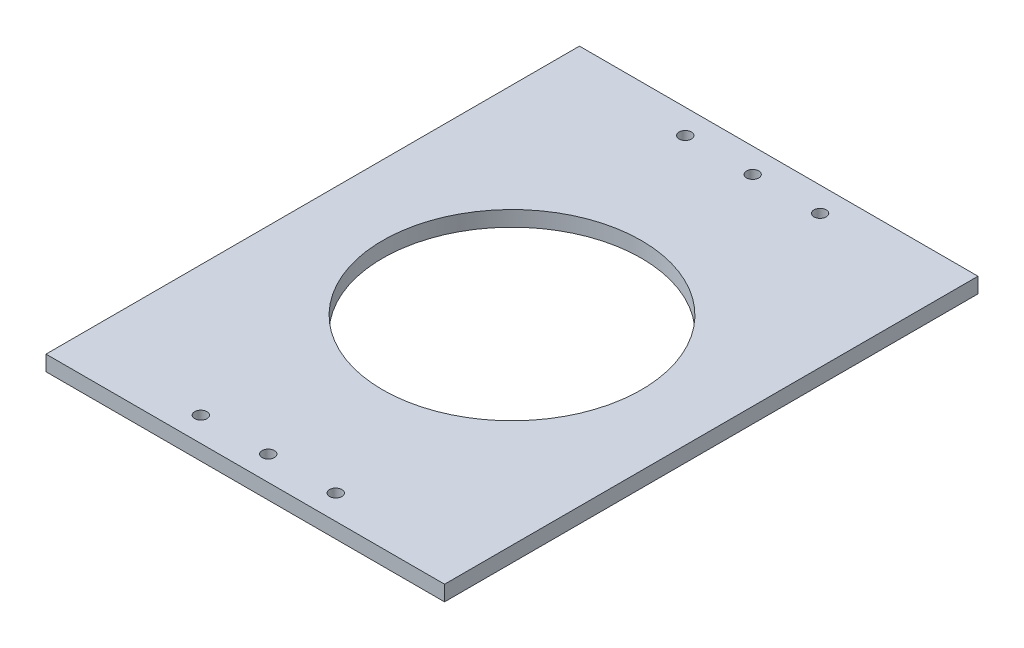
SolidWorks part; units mm, degrees
ref_plane "Front Plane" through (0, 0, 0) normal (0, 0, 1) x (1, 0, 0)
ref_plane "Top Plane" through (0, 0, 0) normal (0, 1, 0) x (1, 0, 0)
ref_plane "Right Plane" through (0, 0, 0) normal (1, 0, 0) x (0, 0, -1)
sketch "Sketch1" plane through (0, 0, 0) normal (0, 1, 0) x (1, 0, 0)
  line L0 (-276.663, 28.4247) -> (-130.5123, 28.4247) construction
  line L1 (-341.663, 115.4247) -> (-211.663, 115.4247)
  line L2 (-341.663, 115.4247) -> (-341.663, -58.5753)
  line L3 (-341.663, -58.5753) -> (-211.663, -58.5753)
  line L4 (-211.663, 115.4247) -> (-211.663, -58.5753)
  line L5 (-341.663, 115.4247) -> (-211.663, -58.5753) construction
  line L6 (-341.663, -58.5753) -> (-211.663, 115.4247) construction
  circle A0 centre (-276.663, 28.4247) radius 42.1979
  circle A1 centre (-299.163, 107.4247) radius 2
  circle A2 centre (-277.163, 107.4247) radius 2
  circle A3 centre (-255.163, 107.4247) radius 2
  circle A4 centre (-255.163, -50.5753) radius 2
  circle A5 centre (-277.163, -50.5753) radius 2
  circle A6 centre (-299.163, -50.5753) radius 2
  point P0 (-276.663, 28.4247)
  dimension "D1" = 174
  dimension "D2" = 130
extrude "Boss-Extrude1" add sketch "Sketch1" along normal blind 5
